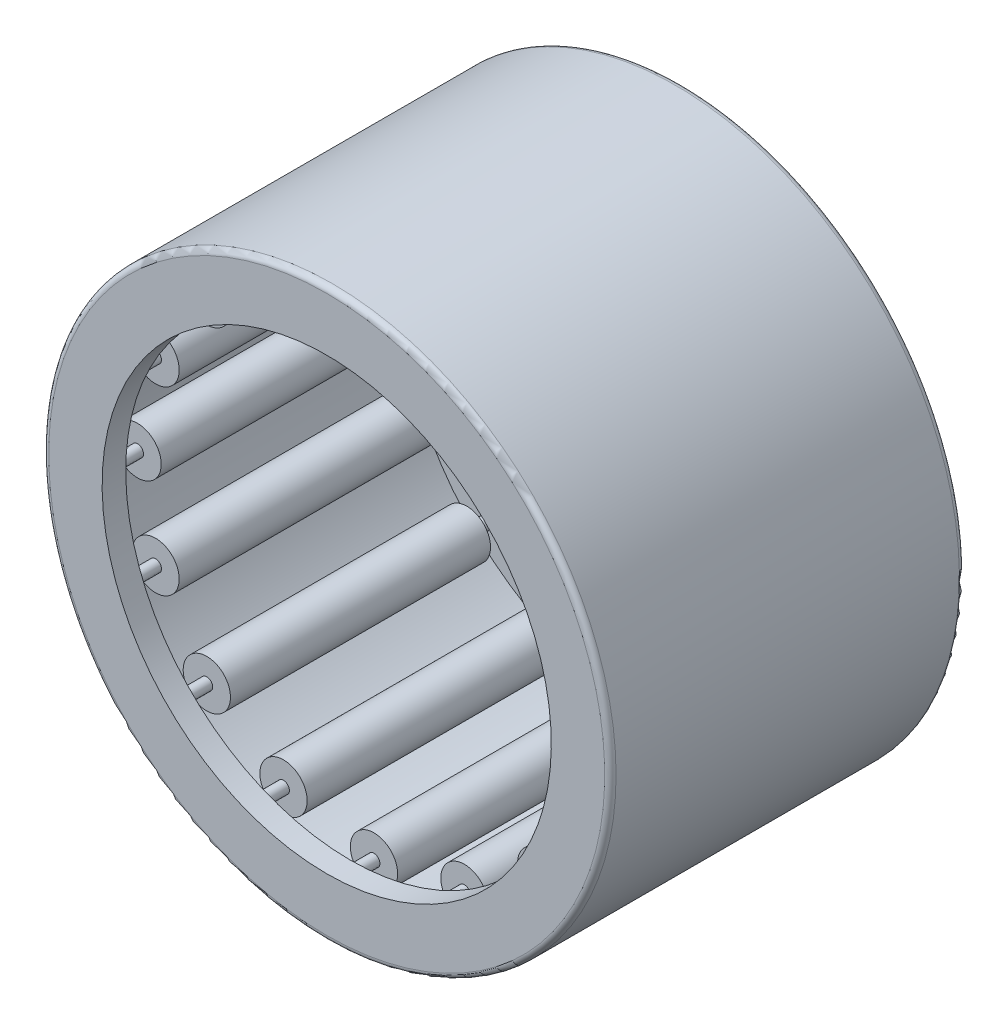
SolidWorks part; units mm, degrees
ref_plane "Front Plane" through (0, 0, 0) normal (0, 0, 1) x (1, 0, 0)
ref_plane "Top Plane" through (0, 0, 0) normal (0, 1, 0) x (1, 0, 0)
ref_plane "Right Plane" through (0, 0, 0) normal (1, 0, 0) x (0, 0, -1)
sketch "Sketch1" plane through (0, 0, 0) normal (1, 0, 0) x (0, 0, -1)
  line L0 (-7.9375, 0) -> (7.9375, 0) construction
  line L1 (0, 0) -> (0, 12.7) construction
  line L2 (-7.9375, 0) -> (-7.9375, 12.7) construction
  line L3 (-7.9375, 12.7) -> (7.9375, 12.7)
  line L4 (7.9375, 12.7) -> (7.9375, 0) construction
  line L5 (7.9375, 0) -> (6.8792, 0) construction
  line L6 (6.8792, 0) -> (6.8792, 11.6417) construction
  line L7 (6.8792, 11.6417) -> (-6.8792, 11.6417)
  line L8 (-6.8792, 11.6417) -> (-6.8792, 0) construction
  line L9 (-6.8792, 0) -> (-7.9375, 0) construction
  line L10 (-7.9375, 12.7) -> (-7.9375, 10.0542)
  line L11 (-7.9375, 10.0542) -> (-6.8792, 10.0542)
  line L12 (-6.8792, 10.0542) -> (-6.8792, 11.6417)
  line L13 (6.8792, 12.7) -> (6.8792, 11.6417) construction
  line L14 (6.8792, 11.6417) -> (6.8792, 10.0542)
  line L15 (6.8792, 10.0542) -> (7.9375, 10.0542)
  line L16 (7.9375, 10.0542) -> (7.9375, 12.7)
  line L17 (6.8792, 11.6417) -> (6.8792, 10.5833) construction
  line L18 (6.8792, 10.5833) -> (6.8792, 9.525) construction
  line L19 (6.8792, -11.6417) -> (6.8792, -10.5833) construction
  line L20 (6.8792, -12.7) -> (6.8792, -11.6417) construction
  line L21 (7.9375, -10.0542) -> (7.9375, -12.7) construction
  line L22 (6.8792, -10.0542) -> (7.9375, -10.0542) construction
  line L23 (6.8792, -11.6417) -> (6.8792, -10.0542) construction
  line L24 (-6.8792, -10.0542) -> (-6.8792, -11.6417) construction
  line L25 (-7.9375, -10.0542) -> (-6.8792, -10.0542) construction
  line L26 (-7.9375, -12.7) -> (-7.9375, -10.0542) construction
  line L27 (6.8792, -11.6417) -> (-6.8792, -11.6417) construction
  line L28 (-7.9375, -12.7) -> (7.9375, -12.7) construction
  point P5 (0, 9.525)
  dimension "Width" = 15.875
  dimension "OD" = 25.4
  dimension "Shaft Dia" = 19.05
revolve "Revolve1" add sketch "Sketch1" angle 360 about L0
sketch "Sketch2" plane through (0, 0, 0) normal (1, 0, 0) x (0, 0, -1)
  line L0 (6.8792, 11.6417) -> (-6.8792, 11.6417) construction
  line L1 (-5.8208, 10.5833) -> (5.8208, 10.5833) construction
  line L2 (-5.8208, 10.5833) -> (-5.8208, 11.6417) construction
  line L3 (-5.8208, 11.6417) -> (5.8208, 11.6417)
  line L4 (5.8208, 10.5833) -> (5.8208, 11.6417) construction
  line L5 (6.8792, 10.0542) -> (7.9375, 10.0542) construction
  line L6 (-6.8792, 10.5833) -> (-5.8208, 10.5833) construction
  line L7 (5.8208, 10.5833) -> (6.8792, 10.5833) construction
  line L8 (-7.9375, 10.0542) -> (-6.8792, 10.0542) construction
  line L9 (-5.8208, 10.8479) -> (-5.8208, 10.3188) construction
  line L10 (-6.8792, 10.5833) -> (-6.8792, 10.0542) construction
  line L11 (-5.8208, 11.6417) -> (-5.8208, 10.8479)
  line L12 (5.8208, 11.6417) -> (5.8208, 10.8479)
  line L13 (5.8208, 10.8479) -> (-5.8208, 10.8479)
  line L14 (0, 11.6417) -> (0, 9.525) construction
  line L15 (-6.8792, 10.0542) -> (-6.8792, 11.6417) construction
  line L16 (-5.8208, 10.3188) -> (-6.8792, 10.3188) construction
  line L17 (0, 0) -> (7.9375, 0) construction
  line L18 (-5.8208, -10.3188) -> (-6.8792, -10.3188) construction
  line L19 (0, -11.6417) -> (0, -9.525) construction
  line L20 (-6.8792, -10.5833) -> (-6.8792, -10.0542) construction
  line L21 (-5.8208, -10.8479) -> (-5.8208, -10.3188) construction
  line L22 (5.8208, -10.5833) -> (6.8792, -10.5833) construction
  line L23 (-6.8792, -10.5833) -> (-5.8208, -10.5833) construction
  line L24 (5.8208, -10.5833) -> (5.8208, -11.6417) construction
  line L25 (-5.8208, -10.5833) -> (-5.8208, -11.6417) construction
  line L26 (-5.8208, -10.5833) -> (5.8208, -10.5833) construction
  line L27 (5.8208, -10.8479) -> (-5.8208, -10.8479) construction
  line L28 (5.8208, -11.6417) -> (5.8208, -10.8479) construction
  line L29 (-5.8208, -11.6417) -> (-5.8208, -10.8479) construction
  line L30 (-5.8208, -11.6417) -> (5.8208, -11.6417) construction
  line L31 (7.9375, -12.7) -> (7.9375, 12.7) construction
  point P16 (0, 10.5833)
revolve "Revolve2" add sketch "Sketch2" angle 360 about L1
sketch "Sketch3" plane through (0, 0, 0) normal (1, 0, 0) x (0, 0, -1)
  line L0 (6.8792, 11.6417) -> (6.8792, 10.0542) construction
  line L1 (-6.8792, 10.5833) -> (6.8792, 10.5833)
  line L2 (-6.8792, 10.5833) -> (-6.8792, 10.8479)
  line L3 (-6.8792, 10.8479) -> (6.8792, 10.8479)
  line L4 (6.8792, 10.5833) -> (6.8792, 10.8479)
  line L5 (0, 0) -> (7.9375, 0) construction
  line L6 (7.9375, -12.7) -> (7.9375, 12.7) construction
  line L7 (6.8792, -10.5833) -> (6.8792, -10.8479) construction
  line L8 (-6.8792, -10.8479) -> (6.8792, -10.8479) construction
  line L9 (-6.8792, -10.5833) -> (-6.8792, -10.8479) construction
  line L10 (-6.8792, -10.5833) -> (6.8792, -10.5833) construction
revolve "Revolve3" add sketch "Sketch3" angle 360 about L1
ref_axis "Axis1" through (0, 0, -7.9375) along (0, 0, 1)
pattern_circular "CirPattern1" count 16 every 22.5 about axis through (0, 0, -7.9375) along (0, 0, 1) of bodies 166 167
fillet "Fillet1" radius 0.254 2 edges at (0, -12.7, -7.9375) (0, -12.7, 7.9375)
sketch "Sketch4" plane through (0, 0, 0) normal (1, 0, 0) x (0, 0, -1)
  line L1 (7.6835, 9.525) -> (5.8208, 9.525)
  line L2 (7.6835, 9.525) -> (7.6835, 10.0542)
  line L3 (7.6835, 10.0542) -> (5.8208, 10.0542)
  line L4 (5.8208, 9.525) -> (5.8208, 10.0542)
  line L5 (-7.9375, 10.0542) -> (-6.8792, 10.0542) construction
  line L6 (7.6835, -12.7) -> (7.6835, 12.7) construction
  line L7 (5.8208, 11.6417) -> (5.8208, 10.8479) construction
revolve "Revolve4" [suppressed] add sketch "Sketch4" angle 360 about L0
sketch "Sketch5" plane through (0, 0, 0) normal (1, 0, 0) x (0, 0, -1)
  line L0 (-7.6835, 12.7) -> (-7.6835, -12.7) construction
  line L1 (-5.8208, 9.525) -> (-7.6835, 9.525)
  line L2 (-5.8208, 9.525) -> (-5.8208, 10.0542)
  line L3 (-5.8208, 10.0542) -> (-7.6835, 10.0542)
  line L4 (-7.6835, 9.525) -> (-7.6835, 10.0542)
  line L6 (-5.8208, 11.6417) -> (-5.8208, 10.8479) construction
  line L7 (-7.9375, 10.0542) -> (-6.8792, 10.0542) construction
revolve "Revolve5" [suppressed] add sketch "Sketch5" angle 360 about L0
equation "\"Angle@CirPattern1\" = 360/\"Rollers@CirPattern1\""
equation "\"Rollers@CirPattern1\" = \"OD@Sketch1\"*16"
equation "\"D1@Fillet1\" = \"OD@Sketch1\"*.01"
